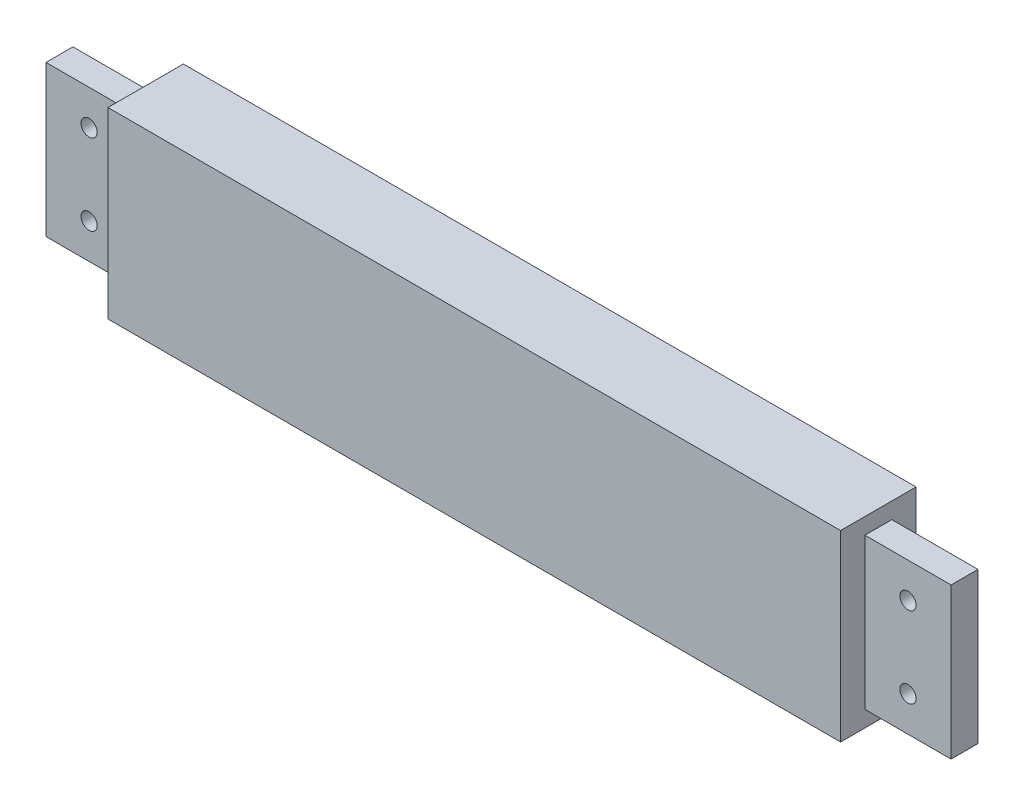
SolidWorks part; units mm, degrees
ref_plane "Front Plane" through (0, 0, 0) normal (0, 0, 1) x (1, 0, 0)
ref_plane "Top Plane" through (0, 0, 0) normal (0, 1, 0) x (1, 0, 0)
ref_plane "Right Plane" through (0, 0, 0) normal (1, 0, 0) x (0, 0, -1)
sketch "Sketch1" plane through (0, 0, 0) normal (0, 0, 1) x (1, 0, 0)
  line L1 (215.9, 53.975) -> (-215.9, 53.975)
  line L2 (215.9, 53.975) -> (215.9, -53.975)
  line L3 (215.9, -53.975) -> (-215.9, -53.975)
  line L4 (-215.9, 53.975) -> (-215.9, -53.975)
  line L5 (215.9, 53.975) -> (-215.9, -53.975) construction
  line L6 (215.9, -53.975) -> (-215.9, 53.975) construction
  point P0 (0, 0)
  dimension "D1" = 107.95
  dimension "D2" = 431.8
extrude "Boss-Extrude1" add sketch "Sketch1" along normal mid plane 44.45
sketch "Sketch2" plane through (215.9, 0, 0) normal (1, 0, 0) x (0, 0, -1)
  line L1 (7.9375, 44.45) -> (-7.9375, 44.45)
  line L2 (7.9375, 44.45) -> (7.9375, -44.45)
  line L3 (7.9375, -44.45) -> (-7.9375, -44.45)
  line L4 (-7.9375, 44.45) -> (-7.9375, -44.45)
  line L5 (7.9375, 44.45) -> (-7.9375, -44.45) construction
  line L6 (7.9375, -44.45) -> (-7.9375, 44.45) construction
  point P0 (0, 0)
  dimension "D1" = 15.875
  dimension "D2" = 88.9
extrude "Boss-Extrude2" add sketch "Sketch2" along normal blind 50.8 contours L4 L3 L2 L1
sketch "Sketch3" plane through (0, 0, 7.9375) normal (0, 0, 1) x (1, 0, 0)
  line L0 (266.7, 44.45) -> (215.9, -44.45) construction
  line L1 (241.3, 0) -> (241.3, 44.45) construction
  line L2 (266.7, 44.45) -> (215.9, 44.45) construction
  circle A0 centre (241.3, 23.8125) radius 4.7625
  circle A1 centre (241.3, -23.8125) radius 4.7625
  dimension "D1" = 9.525
  dimension "D2" = 23.8125
  dimension "D3" = 23.8125
extrude "Cut-Extrude1" cut sketch "Sketch3" against normal through all contours A0 | A1 region at (241.3, 23.8125, 7.9375)
sketch "Sketch4" plane through (215.9, 0, 0) normal (1, 0, 0) x (0, 0, -1)
  line L0 (22.225, 28.575) -> (19.05, 28.575)
  line L1 (22.225, -53.975) -> (22.225, 53.975) construction
  line L2 (19.05, 28.575) -> (19.05, 19.05)
  line L3 (19.05, 19.05) -> (22.225, 19.05)
  line L4 (-22.225, -53.975) -> (22.225, -53.975) construction
  line L5 (22.225, 28.575) -> (22.225, 19.05)
  dimension "D1" = 9.525
  dimension "D2" = 3.175
  dimension "D3" = 73.025
extrude "Cut-Extrude2" cut sketch "Sketch4" against normal through all
mirror "Mirror1" about plane through (0, 0, 0) normal (1, 0, 0) of "Boss-Extrude2", "Cut-Extrude1"
